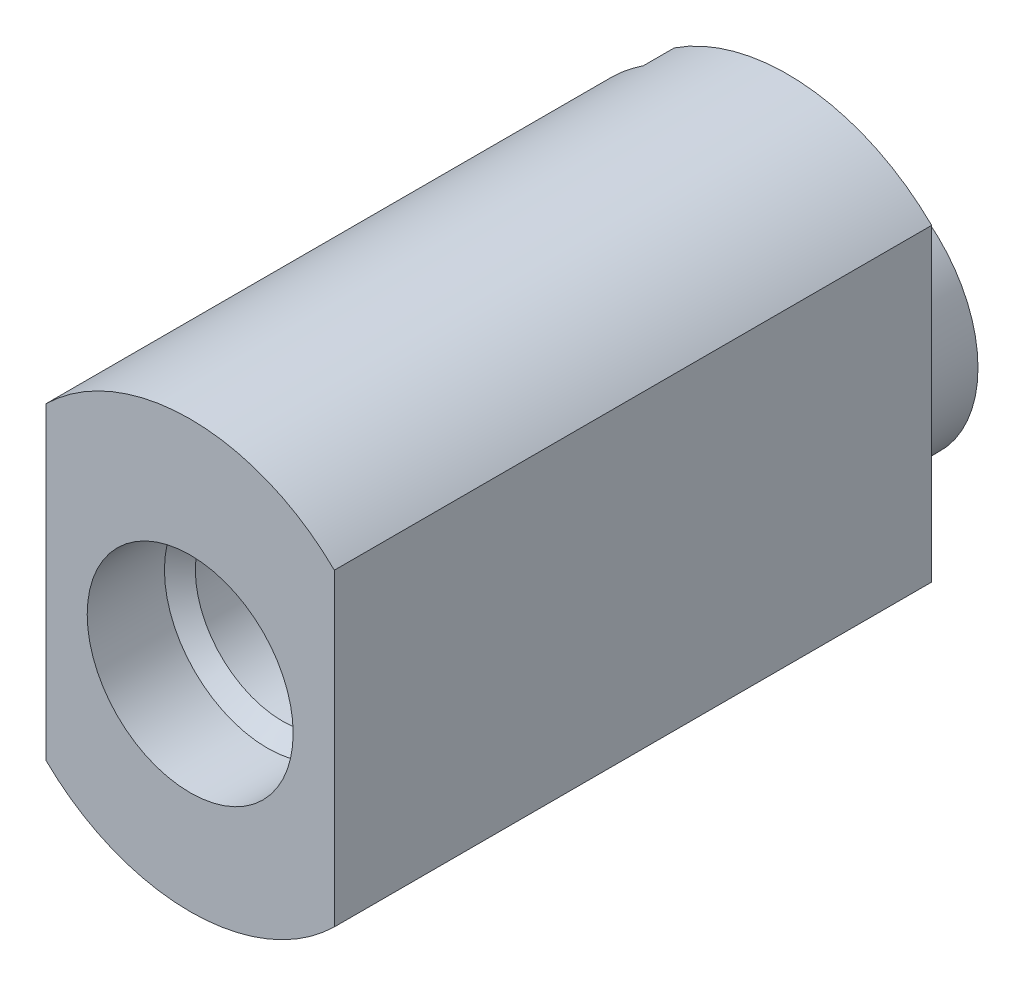
SolidWorks part; units mm, degrees
material "3D printed plastic"
ref_plane "Front Plane" through (0, 0, 0) normal (0, 0, 1) x (1, 0, 0)
ref_plane "Top Plane" through (0, 0, 0) normal (0, 1, 0) x (1, 0, 0)
ref_plane "Right Plane" through (0, 0, 0) normal (1, 0, 0) x (0, 0, -1)
sketch "Sketch1" plane through (0, 0, 0) normal (0, 0, 1) x (1, 0, 0)
  line L0 (-14, 15) -> (-14, -15)
  line L1 (-14, -15) -> (14, -15) construction
  line L2 (14, -15) -> (14, 15)
  line L3 (14, 15) -> (-14, 15) construction
  line L4 (-14, 15) -> (14, -15) construction
  arc A0 (-14, 15) -> (14, 15) centre (0, 0.7171) cw
  arc A1 (-14, -15) -> (14, -15) centre (0, -0.7171) ccw
  circle A2 centre (0, -0.7171) radius 8.5
  dimension "D2" = 17
  dimension "D3" = 20
  dimension "D1" = 28
  dimension "D4" = 30
extrude "Boss-Extrude1" add sketch "Sketch1" along normal blind 58
sketch "Sketch3" plane through (0, 0, 0) normal (0, 0, -1) x (-1, 0, 0)
  line L0 (14, 15) -> (14, -15) construction
  line L1 (11, 28.1009) -> (14, 28.1009)
  line L2 (11, 28.1009) -> (11, -28.9406)
  line L3 (11, -28.9406) -> (14, -28.9406)
  line L4 (14, 28.1009) -> (14, -28.9406)
  dimension "D1" = 3
extrude "Cut-Extrude2" cut sketch "Sketch3" against normal blind 3
sketch "Sketch4" plane through (0, 0, 58) normal (0, 0, 1) x (1, 0, 0)
  circle A0 centre (0, -0.7171) radius 10
  dimension "D1" = 20
extrude "Cut-Extrude3" cut sketch "Sketch4" against normal blind 5
chamfer "Chamfer1" distance 4 angle 45 1 edges at (8.5, -0.7171, 53)
sketch "Sketch5" plane through (0, 0, 0) normal (0, 0, -1) x (-1, 0, 0)
  line L0 (11, 5.22) -> (11, -6.6543)
  line L1 (11, 17.4204) -> (11, -17.4204) construction
  arc A0 (11, 5.22) -> (11, -6.6543) centre (0, -0.7171) ccw
  circle A1 centre (0, -0.7171) radius 9.75
  dimension "D1" = 12.5
  dimension "D2" = 19.5
extrude "Boss-Extrude2" add sketch "Sketch5" along normal blind 6
sketch "Sketch6" plane through (0, 0, 0) normal (0, 0, -1) x (-1, 0, 0)
  line L0 (0, -16.7171) -> (0, 15.2829) construction
  circle A0 centre (0, 15.2829) radius 1.25
  circle A1 centre (0, -16.7171) radius 1.25
  circle A2 centre (0, -0.7171) radius 8.5 construction
  dimension "D2" = 2.5
  dimension "D3" = 16
  dimension "D1" = 32
extrude "Cut-Extrude4" cut sketch "Sketch6" against normal blind 15
